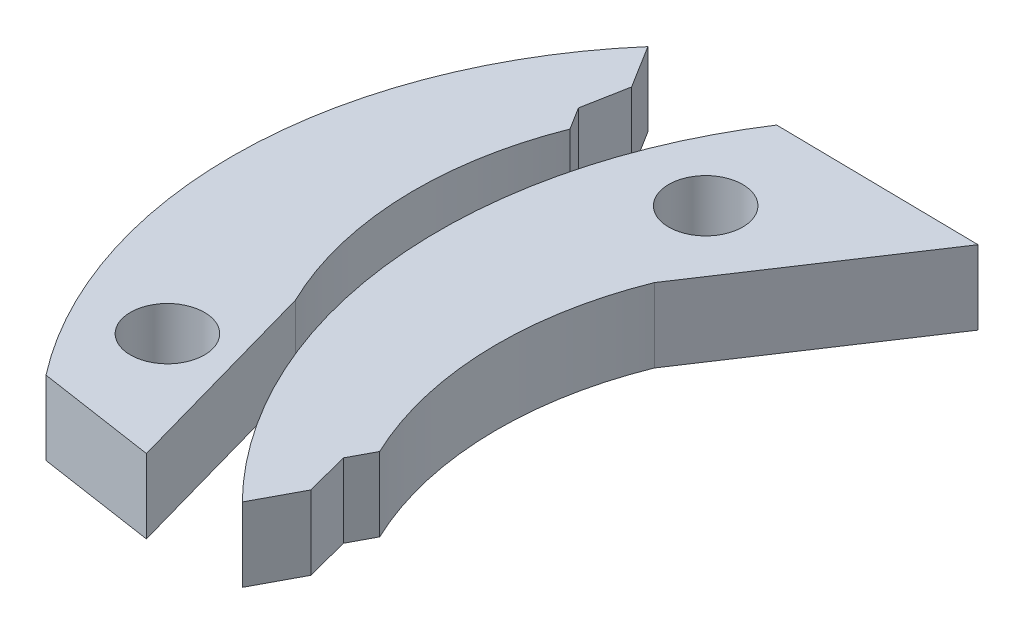
SolidWorks part; units mm, degrees
ref_plane "Front Plane" through (0, 0, 0) normal (0, 0, 1) x (1, 0, 0)
ref_plane "Top Plane" through (0, 0, 0) normal (0, 1, 0) x (1, 0, 0)
ref_plane "Right Plane" through (0, 0, 0) normal (1, 0, 0) x (0, 0, -1)
sketch "Sketch2" plane through (0, 3, 0) normal (0, 1, 0) x (1, 0, 0)
  line L0 (-13.2403, 12.4374) -> (-21.5259, 12.5576)
  line L1 (-13.2403, 12.4374) -> (-18.4726, 4.5436)
  line L2 (-25.1346, -3.3438) -> (-22.7677, -11.7594)
  line L3 (-22.7677, -11.7594) -> (-27.5579, -11.0409)
  line L4 (-18.1098, -6.9576) -> (-18.6204, -7.9158)
  line L5 (-18.6204, -7.9158) -> (-18.157, -9.7041)
  line L6 (-18.157, -9.7041) -> (-19.1229, -11.5166)
  line L8 (-26.8918, 12.6995) -> (-25.805, 10.9567)
  line L9 (-25.805, 10.9567) -> (-26.146, 9.1411)
  line L10 (-26.146, 9.1411) -> (-25.5761, 8.2272)
  line L11 (-18.157, -9.7041) -> (-19.1229, -11.5166)
  arc A0 (-18.4726, 4.5436) -> (-18.1098, -6.9576) centre (-5.129, -0.7918) ccw
  arc A1 (-25.5761, 8.2272) -> (-25.1346, -3.3438) centre (-12.212, 2.9432) ccw
  arc A3 (-21.5259, 12.5576) -> (-19.1229, -11.5166) centre (-5.3712, 2.0131) ccw
  arc A4 (-26.8918, 12.6995) -> (-27.5579, -11.0409) centre (-12.7246, 0.4224) ccw
  circle A5 centre (-20.1294, 8.283) radius 1.5
  circle A6 centre (-26.5518, -7.1229) radius 1.5
  dimension "D1" = 3
  dimension "D2" = 3
  dimension "D3" = 18.7466
  dimension "D4" = 14.3708
  dimension "D5" = 19.2915
  dimension "D6" = 14.3708
  dimension "D7" = 2.0539
  dimension "D8" = 1.8473
  dimension "D9" = 1.8473
  dimension "D10" = 2.0539
  dimension "D11" = 1.0857
  dimension "D12" = 8.2865
  dimension "D13" = 9.4704
  dimension "D14" = 8.7421
  dimension "D15" = 4.8438
extrude "Boss-Extrude2" add sketch "Sketch2" along normal blind 3 contours L8 A4 L3 L2 A1 L10 L9 A6 | L0 A3 L6 L5 L4 A0 L1 A5 region at (-20.5057, 3, -2.5981) region at (-27.8724, 3, 0.4675)
